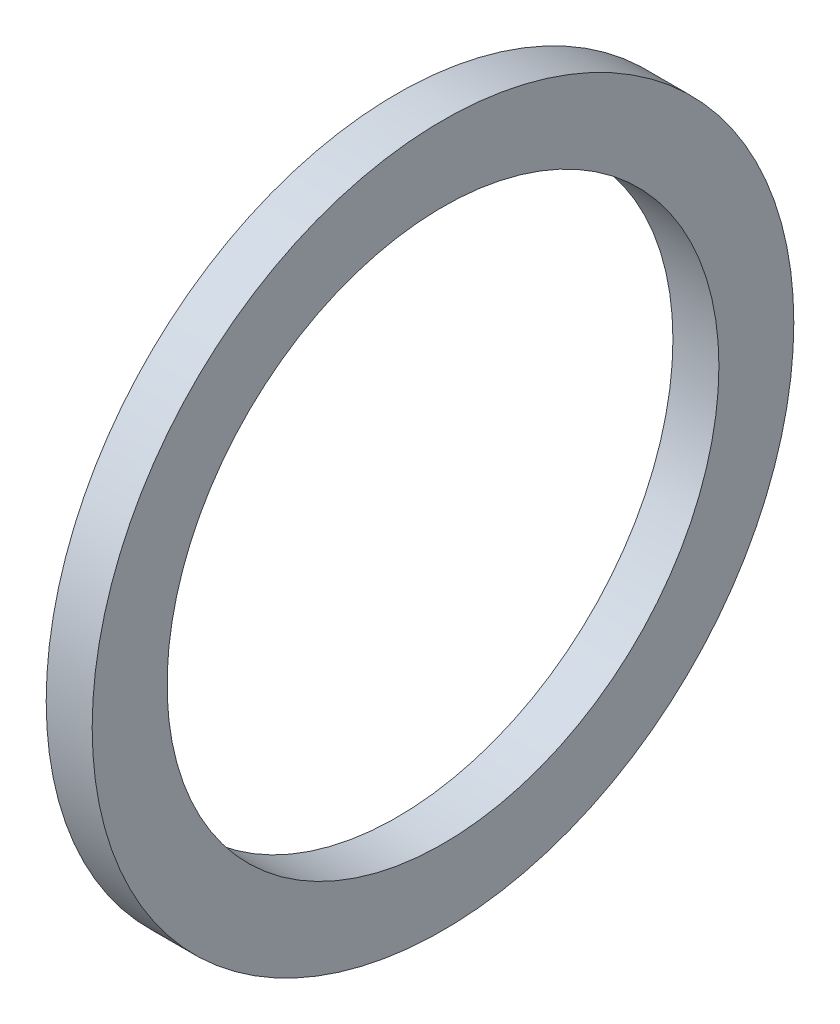
SolidWorks part; units mm, degrees
ref_plane "Front Plane" through (0, 0, 0) normal (0, 0, 1) x (1, 0, 0)
ref_plane "Top Plane" through (0, 0, 0) normal (0, 1, 0) x (1, 0, 0)
ref_plane "Right Plane" through (0, 0, 0) normal (1, 0, 0) x (0, 0, -1)
sketch "Sketch1" plane through (0, 0, 0) normal (1, 0, 0) x (0, 0, -1)
  circle A0 centre (0, 0) radius 76.29
  circle A1 centre (0, 0) radius 60
  dimension "D1" = 152.58
  dimension "D2" = 120
extrude "Boss-Extrude1" add sketch "Sketch1" along normal blind 10
